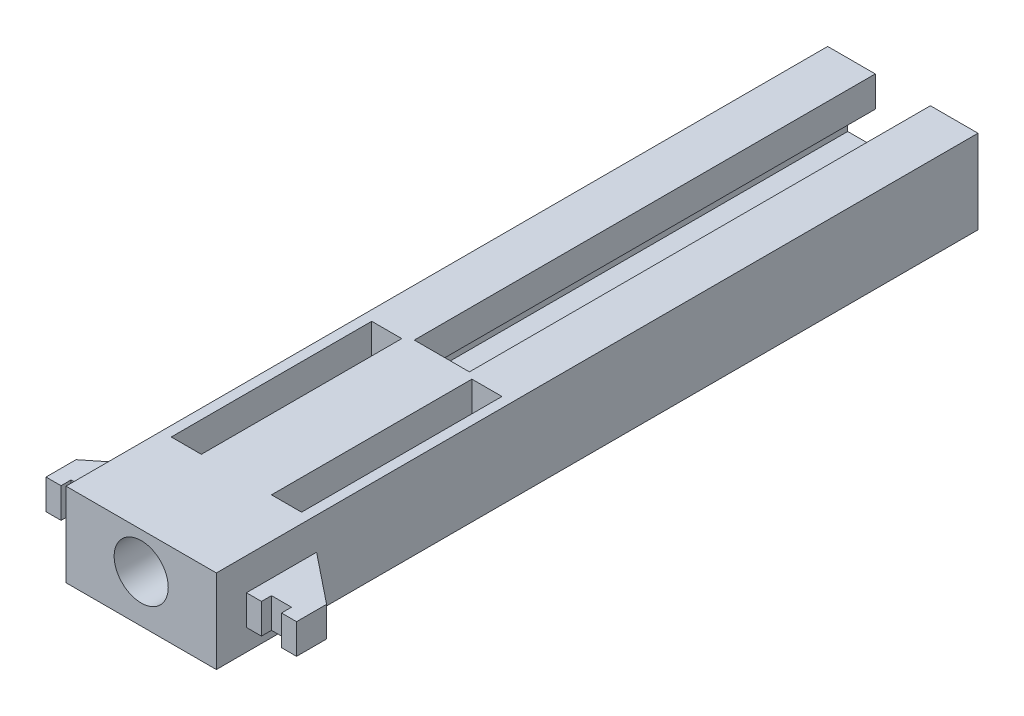
SolidWorks part; units mm, degrees
ref_plane "Front Plane" through (0, 0, 0) normal (0, 0, 1) x (1, 0, 0)
ref_plane "Top Plane" through (0, 0, 0) normal (0, 1, 0) x (1, 0, 0)
ref_plane "Right Plane" through (0, 0, 0) normal (1, 0, 0) x (0, 0, -1)
sketch "Sketch9" plane through (0, 0, 0) normal (0, 0, 1) x (1, 0, 0)
  line L1 (-7.5, 8.35) -> (7.5, 8.35)
  line L2 (-7.5, 8.35) -> (-7.5, 0)
  line L3 (-7.5, 0) -> (7.5, 0)
  line L4 (7.5, 8.35) -> (7.5, 0)
  line L5 (-7.5, 8.35) -> (7.5, 0) construction
  line L6 (-7.5, 0) -> (7.5, 8.35) construction
  point P0 (0, 4.175)
  point P19 (0, 0)
  dimension "D1" = 8.35
  dimension "D2" = 15
extrude "Boss-Extrude4" add sketch "Sketch9" along normal blind 76
sketch "Sketch7" plane through (0, 0, 0) normal (0, 0, 1) x (1, 0, 0)
  line L0 (-5.5, 2) -> (-5.5, 5.3)
  line L1 (-5.5, 5.3) -> (-2.75, 5.3)
  line L2 (-2.75, 5.3) -> (-2.75, 8.35)
  line L3 (-2.75, 8.35) -> (2.75, 8.35) construction
  line L4 (2.75, 8.35) -> (2.75, 5.3)
  line L5 (2.75, 5.3) -> (5.5, 5.3)
  line L6 (5.5, 5.3) -> (5.5, 2)
  line L7 (5.5, 2) -> (-5.5, 2)
  line L9 (7.5, 8.35) -> (-7.5, 8.35) construction
  line L11 (7.5, 0) -> (7.5, 8.35) construction
  line L13 (-2.75, 8.35) -> (2.75, 8.35)
  dimension "D1" = 3.3
  dimension "D2" = 2
  dimension "D3" = 11
  dimension "D4" = 5.5
  dimension "D5" = 2
extrude "Cut-Extrude4" cut sketch "Sketch7" along normal blind 46
sketch "Sketch10" plane through (0, 0, 76) normal (0, 0, 1) x (1, 0, 0)
  line L0 (5.5, 2) -> (-5.5, 2) construction
  circle A0 centre (0, 4.7) radius 2.7
  dimension "D1" = 5.4
extrude "Cut-Extrude5" cut sketch "Sketch10" against normal up to surface (30 mm away) up to face at (0, 5.2375, 46)
sketch "Sketch12" plane through (7.5, 0, 0) normal (1, 0, 0) x (0, 0, -1)
  line L0 (-76, 0) -> (0, 0) construction
  line L1 (-73, 5.14) -> (-70, 5.14)
  line L2 (-73, 5.14) -> (-73, 2.14)
  line L3 (-73, 2.14) -> (-70, 2.14)
  line L4 (-70, 5.14) -> (-70, 2.14)
  line L5 (-73, 5.14) -> (-70, 2.14) construction
  line L6 (-73, 2.14) -> (-70, 5.14) construction
  line L7 (-76, 0) -> (-76, 8.35) construction
  point P0 (-71.5, 3.64)
  dimension "D1" = 3
  dimension "D2" = 3
  dimension "D3" = 2.14
  dimension "D4" = 3
extrude "Boss-Extrude5" add sketch "Sketch12" along normal blind 5
ref_plane "Plane1" through (0, 0, 0) normal (1, 0, 0) x (0, 0, -1)
sketch "Sketch13" plane through (0, 0, 73) normal (0, 0, 1) x (1, 0, 0)
  line L1 (9, 5.14) -> (11, 5.14)
  line L2 (9, 5.14) -> (9, 2.14)
  line L3 (9, 2.14) -> (11, 2.14)
  line L4 (11, 5.14) -> (11, 2.14)
  line L6 (12.5, 5.14) -> (7.5, 5.14) construction
  line L7 (12.5, 2.14) -> (7.5, 2.14) construction
  point P8 (10, 5.14)
  point P9 (10, 5.14)
  dimension "D2" = 2
extrude "Cut-Extrude6" cut sketch "Sketch13" against normal blind 1
mirror "Mirror2" about plane through (0, 0, 0) normal (1, 0, 0) of "Boss-Extrude5"
mirror "Mirror4" about plane through (0, 0, 0) normal (1, 0, 0) of "Cut-Extrude6"
sketch "Sketch14" plane through (0, 5.14, 0) normal (0, 1, 0) x (1, 0, 0)
  line L0 (12.5, -70) -> (7.5, -66)
  line L1 (7.5, -76) -> (7.5, 0) construction
  line L2 (7.5, -66) -> (7.5, -70)
  line L3 (7.5, -70) -> (12.5, -70)
  dimension "D1" = 4
extrude "Boss-Extrude6" add sketch "Sketch14" against normal up to surface (3 mm away) up to face at (10, 2.14, 72)
mirror "Mirror5" about plane through (0, 0, 0) normal (1, 0, 0) of "Boss-Extrude6"
sketch "Sketch15" plane through (0, 8.35, 0) normal (0, 1, 0) x (1, 0, 0)
  line L0 (-7.5, -76) -> (-7.5, 0) construction
  line L1 (-6.5, -66.5) -> (-3.5, -66.5)
  line L2 (-6.5, -66.5) -> (-6.5, -46.5)
  line L3 (-6.5, -46.5) -> (-3.5, -46.5)
  line L4 (-3.5, -66.5) -> (-3.5, -46.5)
  line L5 (-6.5, -66.5) -> (-3.5, -46.5) construction
  line L6 (-6.5, -46.5) -> (-3.5, -66.5) construction
  line L7 (2.75, -46) -> (-2.75, -46) construction
  point P0 (-5, -56.5)
  point P11 (-5, -46.5)
  dimension "D1" = 20
  dimension "D2" = 3
  dimension "D3" = 1
  dimension "D4" = 0.5
extrude "Cut-Extrude7" cut sketch "Sketch15" against normal up to next
mirror "Mirror6" about plane through (0, 0, 0) normal (1, 0, 0) of "Cut-Extrude7"
sketch "Sketch16" plane through (0, 0, 0) normal (0, -1, 0) x (1, 0, 0)
  line L0 (0, -35.8636) -> (0, 35.8636) construction
  line L1 (-7.5, 76) -> (7.5, 76) construction
  circle A0 centre (0, 69) radius 2.5
  dimension "D1" = 5
  dimension "D2" = 7
extrude "Cut-Extrude8" cut sketch "Sketch16" against normal up to surface (2 mm away) up to face at (2.7, 4.7, 76)
